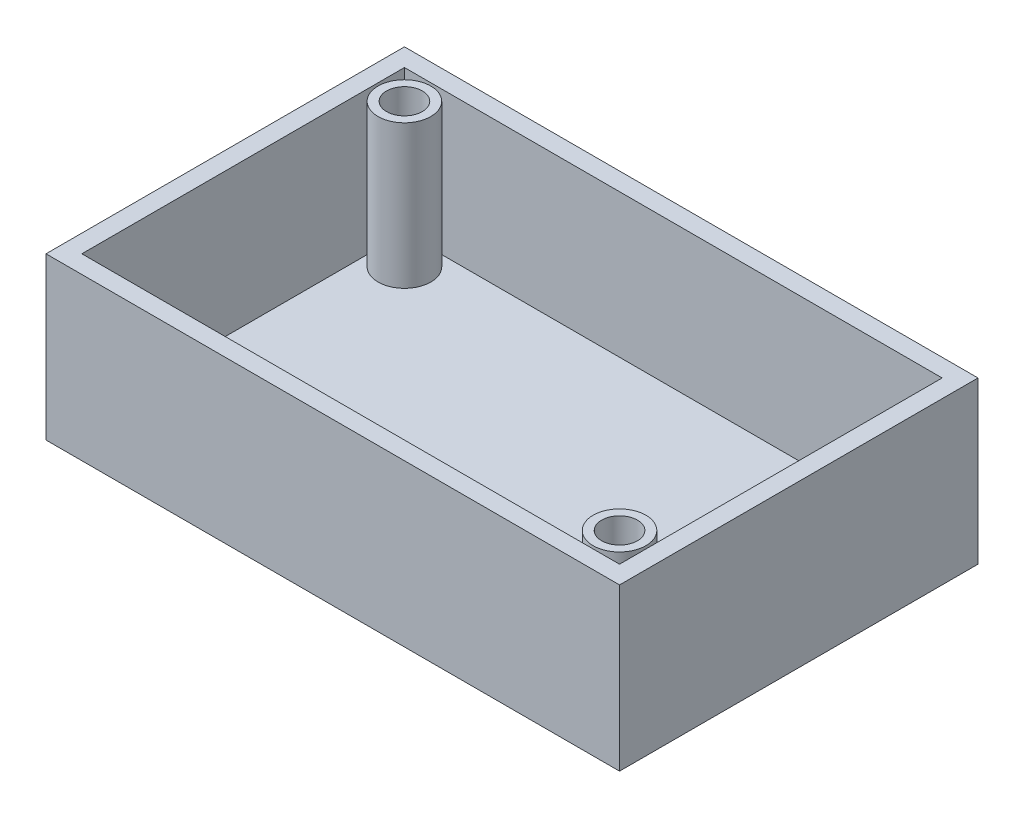
SolidWorks part; units mm, degrees
ref_plane "Front" through (0, 0, 0) normal (0, 0, 1) x (1, 0, 0)
ref_plane "Top" through (0, 0, 0) normal (0, 1, 0) x (1, 0, 0)
ref_plane "Right" through (0, 0, 0) normal (1, 0, 0) x (0, 0, -1)
sketch "Sketch1" plane through (0, 0, 0) normal (0, 1, 0) x (1, 0, 0)
  line L1 (-39.0769, 55.5451) -> (62.5231, 55.5451)
  line L2 (-39.0769, 55.5451) -> (-39.0769, -7.9549)
  line L3 (-39.0769, -7.9549) -> (62.5231, -7.9549)
  line L4 (62.5231, 55.5451) -> (62.5231, -7.9549)
  dimension "D1" = 63.5
  dimension "D2" = 101.6
extrude "Boss-Extrude1" add sketch "Sketch1" along normal blind 3.175
sketch "Sketch2" plane through (0, 3.175, 0) normal (0, 1, 0) x (1, 0, 0)
  line L12 (-35.9019, -4.7799) -> (59.3481, -4.7799)
  line L13 (-35.9019, 52.3701) -> (-35.9019, -4.7799)
  line L14 (59.3481, 52.3701) -> (-35.9019, 52.3701)
  line L15 (59.3481, -4.7799) -> (59.3481, 52.3701)
  line L16 (-35.9019, -4.7799) -> (59.3481, -4.7799)
  line L17 (-35.9019, 52.3701) -> (-35.9019, -4.7799)
  line L18 (59.3481, 52.3701) -> (-35.9019, 52.3701)
  line L19 (59.3481, -4.7799) -> (59.3481, 52.3701)
  line L24 (-39.0769, 55.5451) -> (-39.0769, -7.9549)
  line L25 (-39.0769, -7.9549) -> (62.5231, -7.9549)
  line L26 (62.5231, -7.9549) -> (62.5231, 55.5451)
  line L27 (62.5231, 55.5451) -> (-39.0769, 55.5451)
  line L28 (-39.0769, 55.5451) -> (-39.0769, -7.9549)
  line L29 (-39.0769, -7.9549) -> (62.5231, -7.9549)
  line L30 (62.5231, -7.9549) -> (62.5231, 55.5451)
  line L31 (62.5231, 55.5451) -> (-39.0769, 55.5451)
  dimension "D1" = 3.175
  dimension "D2" = 0
extrude "Boss-Extrude3" add sketch "Sketch2" along normal blind 25.4
sketch "Sketch3" plane through (0, 0, 0) normal (0, -1, 0) x (1, 0, 0)
  circle A0 centre (47.8144, -23.7773) radius 2.1411
extrude "Cut-Extrude1" cut sketch "Sketch3" against normal blind 3.175
ref_plane "Plane1" through (62.5231, 28.575, -55.5451) normal (-1, 0, 0) x (0, 0, 1)
sketch "Sketch5" plane through (0, 3.175, 0) normal (0, 1, 0) x (1, 0, 0)
  line L0 (-35.9019, 52.3701) -> (-35.9019, -4.7799) construction
  line L1 (59.3481, 52.3701) -> (-35.9019, 52.3701) construction
  line L10 (-35.9019, 52.3701) -> (-35.9019, -4.7799)
  line L11 (-35.9019, -4.7799) -> (59.3481, -4.7799)
  line L12 (59.3481, -4.7799) -> (59.3481, 52.3701)
  line L13 (59.3481, 52.3701) -> (-35.9019, 52.3701)
  line L14 (-35.9019, 52.3701) -> (-35.9019, -4.7799)
  line L15 (-35.9019, -4.7799) -> (59.3481, -4.7799)
  line L16 (59.3481, -4.7799) -> (59.3481, 52.3701)
  line L17 (59.3481, 52.3701) -> (-35.9019, 52.3701)
  circle A0 centre (54.1681, 0.4001) radius 3.175
  circle A1 centre (-30.7269, 47.1901) radius 3.175
  circle A2 centre (-30.7269, 47.1901) radius 4.675
  circle A3 centre (54.1681, 0.4001) radius 4.675
  dimension "D2" = 6.35
  dimension "D6" = 6.35
  dimension "D1" = 5.175
  dimension "D3" = 5.18
  dimension "D7" = 5.18
  dimension "D8" = 5.18
  dimension "D4" = 0
  dimension "D5" = 1.5
  dimension "D9" = 1.5
extrude "Boss-Extrude4" add sketch "Sketch5" along normal blind 25.4 contours A2 A1 | A3 A0 region at (-35.2697, 3.175, -47.1901) region at (49.6253, 3.175, -0.4001)
